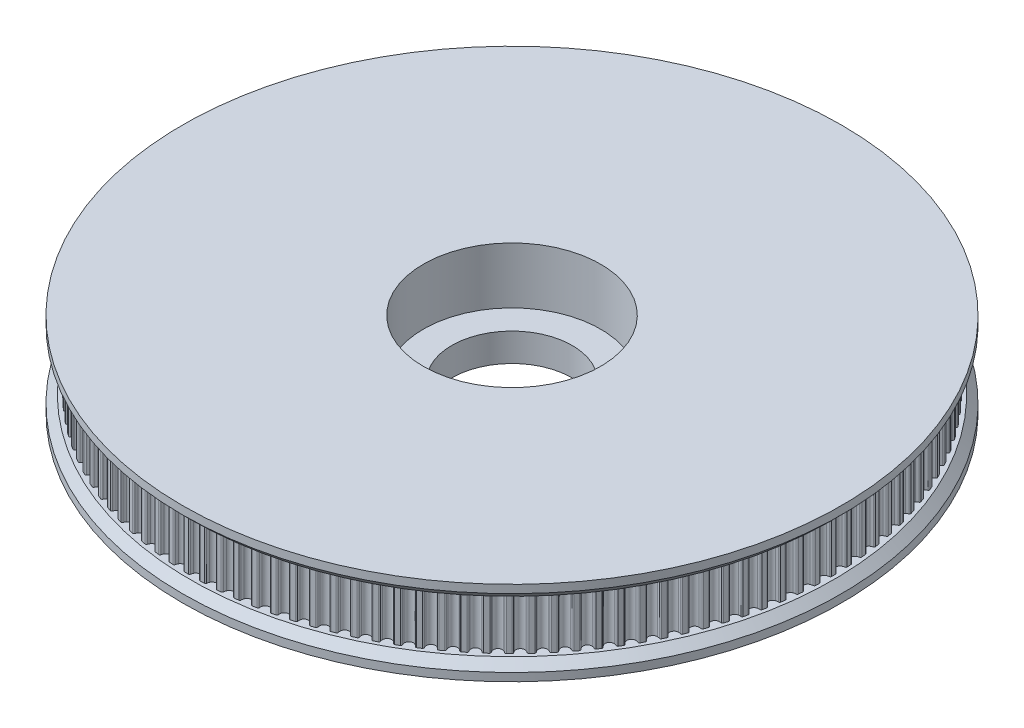
SolidWorks part; units mm, degrees
ref_plane "Plan de face" through (0, 0, 0) normal (0, 0, 1) x (1, 0, 0)
ref_plane "Plan de dessus" through (0, 0, 0) normal (0, 1, 0) x (1, 0, 0)
ref_plane "Plan de droite" through (0, 0, 0) normal (1, 0, 0) x (0, 0, -1)
sketch "Sketch1" plane through (0, 0, 0) normal (0, 1, 0) x (1, 0, 0)
  line L0 (0, 0) -> (0, 39.7887) construction
  line L1 (0, 0) -> (0.9999, 39.7762) construction
  circle A0 centre (0, 0) radius 39.7887 construction
  circle A1 centre (0, 0) radius 39.5347 construction
  circle A2 centre (0, 0) radius 38.7847
  arc A3 (0.4826, 39.0993) -> (0.9747, 38.7725) centre (0.9886, 39.3273) ccw
  arc A4 (0.4826, 39.0993) -> (0.4004, 39.4004) centre (1.3943, 39.5101) cw
  arc A5 (-0.2522, 39.5339) -> (0.2522, 39.5339) centre (0, 0) cw
  arc A6 (0.2522, 39.5339) -> (0.4004, 39.4004) centre (0.2513, 39.3839) cw
  arc A7 (-0.4826, 39.0993) -> (-0.9747, 38.7725) centre (-0.9886, 39.3273) cw
  arc A8 (-0.4826, 39.0993) -> (-0.4004, 39.4004) centre (-1.3943, 39.5101) ccw
  arc A9 (-0.2522, 39.5339) -> (-0.4004, 39.4004) centre (-0.2513, 39.3839) ccw
  arc A10 (-0.9747, 38.7725) -> (0.9747, 38.7725) centre (0, 0) cw
  dimension "D2" = 79.0695
  dimension "D1" = 79.5775
  dimension "D6" = 0.555
  dimension "D5" = 77.5695
  dimension "D7" = 1
  dimension "D8" = 0.15
  dimension "D3" = 1.44
extrude "Boss-Extrude1" add sketch "Sketch1" against normal mid plane 6.5 contours A2
extrude "Boss-Extrude2" add sketch "Sketch1<5>" along normal mid plane 6.5 contours A4 A6 A5 A9 A8 A7 A10 A3
sketch "Sketch1<5>" plane through (0, 0, 0) normal (0, 1, 0) x (1, 0, 0) same geometry as "Sketch1"
pattern_circular "CirPattern1" count 125 every 2.88 about axis through (0, -3.25, 0) along (0, 1, 0) of "Boss-Extrude2" reverse direction yes
sketch "Sketch2" plane through (0, 3.25, 0) normal (0, 1, 0) x (1, 0, 0)
  circle A0 centre (0, 0) radius 41
  dimension "D1" = 82
extrude "Boss-Extrude3" add sketch "Sketch2" along normal blind 2 contours A0
sketch "Sketch3" plane through (0, -3.25, 0) normal (0, -1, 0) x (1, 0, 0)
  circle A0 centre (0, 0) radius 41
  circle A1 centre (0, 0) radius 41 construction
extrude "Boss-Extrude4" add sketch "Sketch3" along normal blind 2
chamfer "Chamfer1" distance 1 angle 45 2 edges at (0, 3.25, 41) (0, -3.25, -41)
sketch "Sketch4" plane through (0, 5.25, 0) normal (0, 1, 0) x (1, 0, 0)
  circle A0 centre (0, 0) radius 7.5
  circle A1 centre (0, 0) radius 11.025
  dimension "D1" = 15
  dimension "D2" = 22.05
extrude "Cut-Extrude2" cut sketch "Sketch4" against normal through all contours A0
extrude "Cut-Extrude3" cut sketch "Sketch4<4>" against normal blind 7 contours A1
sketch "Sketch4<4>" plane through (0, 5.25, 0) normal (0, 1, 0) x (1, 0, 0) same geometry as "Sketch4"
equation "\"NumTeeth\"= 125"
equation "\"ToothPitch\"= 2mm"
equation "\"PulleyDia\"= \"NumTeeth\" * \"ToothPitch\" / 3.1415926536"
equation "\"ToothAngle\"= 360deg / \"NumTeeth\" * 1deg"
equation "\"TransOffsetAngle\"= \"ToothAngle\" / 5 + 0.001"
equation "\"ShoulderRadius\"= 0.15mm"
equation "\"RootRadius\"= 0.555mm"
equation "\"TransRadius\"= 1mm"
equation "\"PLD\"= 0.254mm"
equation "\"PulleyThickness\"= 6.5"
equation "\"TransOffsetDia\"= \"PulleyDia\" - 0.254 * 2"
equation "\"D1@Sketch1\"=\"PulleyDia\""
equation "\"D2@Sketch1\"=\"TransOffsetDia\""
equation "\"ToothBottomDia\"= \"TransOffsetDia\" - 0.75 * 2"
equation "\"D5@Sketch1\"=\"ToothBottomDia\""
equation "\"D3@Sketch1\"=\"ToothAngle\"/2"
equation "\"D6@Sketch1\"=\"RootRadius\""
equation "\"D7@Sketch1\"=\"TransRadius\""
equation "\"D8@Sketch1\"=\"ShoulderRadius\""
equation "\"D1@Boss-Extrude1\"=\"PulleyThickness\""
equation "\"D2@CirPattern1\"=\"ToothAngle\""
equation "\"D1@CirPattern1\"=\"NumTeeth\""
equation "\"D1@Boss-Extrude2\"=\"PulleyThickness\""
